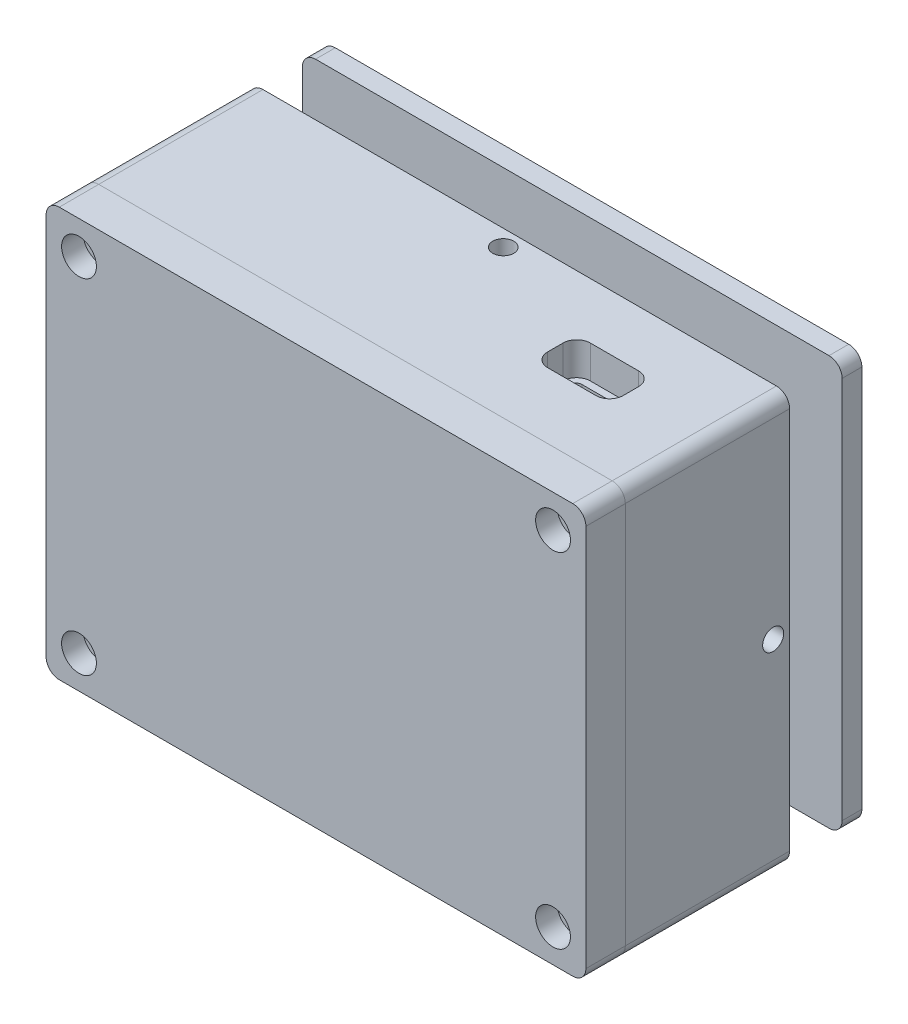
SolidWorks part; units mm, degrees
note: The reader was unsure of these and kept them because the rebuilt part matched: shared geometry of "Sketch8<2>".
ref_plane "Front Plane" through (0, 0, 0) normal (0, 0, 1) x (1, 0, 0)
ref_plane "Top Plane" through (0, 0, 0) normal (0, 1, 0) x (1, 0, 0)
ref_plane "Right Plane" through (0, 0, 0) normal (1, 0, 0) x (0, 0, -1)
sketch "Sketch1" plane through (0, 0, 0) normal (0, 0, 1) x (1, 0, 0)
  line L0 (-52.3117, 23.3251) -> (-52.3117, -26.6749)
  line L1 (-52.3117, -26.6749) -> (17.6883, -26.6749)
  line L2 (17.6883, -26.6749) -> (17.6883, 23.3251)
  line L3 (17.6883, 23.3251) -> (-52.3117, 23.3251)
  dimension "D1" = 50
  dimension "D2" = 70
extrude "Boss-Extrude1" add sketch "Sketch1" along normal blind 2
sketch "Sketch2" plane through (0, 0, 2) normal (0, 0, 1) x (1, 0, 0)
  line L0 (-42.7906, 27.3251) -> (-53.3117, 9.1507)
  line L1 (-53.3117, 9.1507) -> (12.0295, -28.6749)
  line L2 (12.0295, -28.6749) -> (22.5506, -10.5005)
  line L3 (22.5506, -10.5005) -> (-42.7906, 27.3251)
  line L4 (-52.3117, 23.3251) -> (-52.3117, -26.6749) construction
  line L5 (17.6883, 23.3251) -> (-52.3117, 23.3251) construction
  line L7 (-52.3117, -26.6749) -> (17.6883, -26.6749) construction
  dimension "D1" = 21
  dimension "D2" = 75.5
  dimension "D3" = 1
  dimension "D4" = 4
  dimension "D5" = 2
extrude "Boss-Extrude2" add sketch "Sketch2" along normal blind 21
sketch "Sketch3" plane through (0, 0, 0) normal (0, 0, -1) x (-1, 0, 0)
  line L0 (-22.6795, 27.4751) -> (-22.6795, -28.8149)
  line L1 (-22.6795, -28.8149) -> (53.4617, -28.8149)
  line L2 (53.4617, -28.8149) -> (53.4617, 27.4751)
  line L3 (53.4617, 27.4751) -> (-22.6795, 27.4751)
  dimension "D1" = 0.129
  dimension "D2" = 0.14
  dimension "D3" = 0.15
  dimension "D4" = 0.15
extrude "Extrude-Thin1" add sketch "Sketch3" along normal blind 10 and the other way blind 23 separate body thin
sketch "Sketch4" plane through (0, 0, 23) normal (0, 0, 1) x (1, 0, 0)
  line L0 (-42.7906, 27.3251) -> (-53.3117, 9.1507)
  line L1 (-53.3117, 9.1507) -> (12.0295, -28.6749)
  line L2 (12.0295, -28.6749) -> (22.5506, -10.5005)
  line L3 (22.5506, -10.5005) -> (-42.7906, 27.3251)
  line L4 (-53.4617, 27.4751) -> (-53.4617, -28.8149)
  line L5 (-53.4617, -28.8149) -> (22.6795, -28.8149)
  line L6 (22.6795, -28.8149) -> (22.6795, 27.4751)
  line L7 (22.6795, 27.4751) -> (22.6795, -28.8149) construction
  line L8 (22.6795, 27.4751) -> (-53.4617, 27.4751)
extrude "Boss-Extrude3" add sketch "Sketch4" against normal blind 6
fillet "Fillet1" radius 2 4 edges at (25.6795, 30.4751, 6.5) (25.6795, -31.8149, 6.5) (-56.4617, -31.8149, 6.5) (-56.4617, 30.4751, 6.5)
sketch "Sketch5" plane through (0, 0, -10) normal (0, 0, -1) x (-1, 0, 0)
  line L4 (-25.6795, 28.4751) -> (-25.6795, -29.8149) construction
  line L5 (-25.6795, 28.4751) -> (-25.6795, -29.8149)
  line L6 (54.4617, 30.4751) -> (-23.6795, 30.4751) construction
  line L7 (54.4617, 30.4751) -> (-23.6795, 30.4751)
  line L8 (56.4617, -29.8149) -> (56.4617, 28.4751) construction
  line L9 (56.4617, -29.8149) -> (56.4617, 28.4751)
  line L10 (-23.6795, -31.8149) -> (54.4617, -31.8149) construction
  line L11 (-23.6795, -31.8149) -> (54.4617, -31.8149)
  arc A0 (-23.6795, 30.4751) -> (-25.6795, 28.4751) centre (-23.6795, 28.4751) ccw construction
  arc A1 (-23.6795, 30.4751) -> (-25.6795, 28.4751) centre (-23.6795, 28.4751) ccw
  arc A2 (56.4617, 28.4751) -> (54.4617, 30.4751) centre (54.4617, 28.4751) ccw construction
  arc A3 (56.4617, 28.4751) -> (54.4617, 30.4751) centre (54.4617, 28.4751) ccw
  arc A4 (54.4617, -31.8149) -> (56.4617, -29.8149) centre (54.4617, -29.8149) ccw construction
  arc A5 (54.4617, -31.8149) -> (56.4617, -29.8149) centre (54.4617, -29.8149) ccw
  arc A6 (-25.6795, -29.8149) -> (-23.6795, -31.8149) centre (-23.6795, -29.8149) ccw construction
  arc A7 (-25.6795, -29.8149) -> (-23.6795, -31.8149) centre (-23.6795, -29.8149) ccw
extrude "Boss-Extrude4" add sketch "Sketch5" along normal blind 3 separate body
sketch "Sketch6" plane through (0, 0, 17) normal (0, 0, -1) x (-1, 0, 0)
  line L0 (-16.6795, 27.4751) -> (-22.6795, 22.5325)
  line L1 (-22.6795, 27.4751) -> (53.4617, 27.4751) construction
  line L2 (-22.6795, 27.4751) -> (-22.6795, -28.8149) construction
  line L3 (-22.6795, 22.5325) -> (-22.6795, 27.4751)
  line L4 (-22.6795, 27.4751) -> (-16.6795, 27.4751)
  line L5 (42.7906, 27.3251) -> (53.3117, 9.1507)
  line L6 (53.3117, 9.1507) -> (53.4617, 27.4751)
  line L8 (-12.0295, -28.6749) -> (-22.5506, -10.5005)
  line L11 (53.4617, -25.8149) -> (-7.0891, -25.8149)
  line L12 (53.4617, -28.8149) -> (53.4617, 27.4751) construction
  line L13 (53.3117, 9.1507) -> (-12.0295, -28.6749) construction
  line L15 (53.4617, -28.8149) -> (53.4617, -25.8149)
  line L16 (53.4617, -28.8149) -> (-22.6795, -28.8149) construction
  line L18 (-22.6795, -28.8149) -> (53.4617, -28.8149)
  line L19 (-7.0891, -25.8149) -> (-12.0295, -28.6749)
  line L20 (-22.5506, -10.5005) -> (-22.6795, -10.5005)
  line L21 (-22.6795, -10.5005) -> (-22.6795, -28.8149)
  line L22 (42.7906, 27.3251) -> (42.7906, 27.4751)
  line L23 (42.7906, 27.4751) -> (53.4617, 27.4751)
  dimension "D1" = 6
  dimension "D2" = 3
extrude "Boss-Extrude8" add sketch "Sketch6" along normal blind 10
sketch "Sketch7" plane through (0, 0, -10) normal (0, 0, -1) x (-1, 0, 0)
  line L0 (-28.6149, 33.2878) -> (-28.6149, -37.3908)
  line L1 (-28.6149, -37.3908) -> (75.8219, -37.3908)
  line L2 (75.8219, -37.3908) -> (71.6241, 45.1665)
  line L3 (71.6241, 45.1665) -> (-28.6149, 33.2878)
extrude "Cut-Extrude1" cut sketch "Sketch7" against normal blind 8
sketch "Sketch8" plane through (0, 30.4751, 0) normal (0, 1, 0) x (1, 0, 0)
  line L0 (1.7795, -8.5741) -> (1.7795, -10.9259)
  line L1 (3.8536, -13) -> (11.2055, -13)
  line L2 (13.2795, -10.9259) -> (13.2795, -8.5741)
  line L3 (11.2055, -6.5) -> (3.8536, -6.5)
  line L4 (-54.4617, -23) -> (23.6795, -23) construction
  line L6 (25.6795, 2) -> (25.6795, -23) construction
  arc A0 (11.2055, -13) -> (13.2795, -10.9259) centre (11.2055, -10.9259) ccw
  arc A1 (13.2795, -8.5741) -> (11.2055, -6.5) centre (11.2055, -8.5741) ccw
  arc A2 (3.8536, -13) -> (1.7795, -10.9259) centre (3.8536, -10.9259) cw
  arc A3 (3.8536, -6.5) -> (1.7795, -8.5741) centre (3.8536, -8.5741) ccw
  point P12 (13.2795, -6.5)
  point P15 (1.7795, -13)
  point P18 (1.7795, -6.5)
  dimension "D5" = 2.0741
  dimension "D6" = 2.0741
  dimension "D7" = 2.0741
  dimension "D8" = 2.0741
  dimension "D1" = 11.5
  dimension "D2" = 6.5
  dimension "D3" = 10
  dimension "D4" = 12.4
extrude "Cut-Extrude2" cut sketch "Sketch8" against normal blind 8
extrude "Extrude-Thin2" add sketch "Sketch8<2>" against normal blind 6 thin
sketch "Sketch8<2>" plane through (0, 30.4751, 0) normal (0, 1, 0) x (1, 0, 0) same geometry as "Sketch8"
sketch "Sketch10" plane through (0, 27.4751, 0) normal (0, -1, 0) x (1, 0, 0)
  line L0 (1.7795, 9.75) -> (13.2795, 9.75) construction
  line L1 (1.7795, 8.5741) -> (1.7795, 10.9259) construction
  line L2 (13.2795, 10.9259) -> (13.2795, 8.5741) construction
  line L3 (7.5295, 13) -> (7.5295, 6.5) construction
  line L4 (3.8536, 13) -> (11.2055, 13) construction
  line L5 (11.2055, 6.5) -> (3.8536, 6.5) construction
  line L6 (3.6795, 11.9) -> (11.3795, 11.9)
  line L7 (12.3795, 10.9) -> (12.3795, 8.6)
  line L8 (11.3795, 7.6) -> (3.6795, 7.6)
  line L9 (2.6795, 8.6) -> (2.6795, 10.9)
  line L10 (1.7795, 8.5741) -> (1.7795, 10.9259)
  line L11 (11.2055, 6.5) -> (3.8536, 6.5)
  line L12 (13.2795, 10.9259) -> (13.2795, 8.5741)
  line L13 (3.8536, 13) -> (11.2055, 13)
  arc A0 (1.7795, 8.5741) -> (3.8536, 6.5) centre (3.8536, 8.5741) ccw construction
  arc A1 (11.2055, 6.5) -> (13.2795, 8.5741) centre (11.2055, 8.5741) ccw construction
  arc A2 (13.2795, 10.9259) -> (11.2055, 13) centre (11.2055, 10.9259) ccw construction
  arc A3 (3.8536, 13) -> (1.7795, 10.9259) centre (3.8536, 10.9259) ccw construction
  arc A4 (1.7795, 8.5741) -> (3.8536, 6.5) centre (3.8536, 8.5741) ccw
  arc A5 (11.2055, 6.5) -> (13.2795, 8.5741) centre (11.2055, 8.5741) ccw
  arc A6 (13.2795, 10.9259) -> (11.2055, 13) centre (11.2055, 10.9259) ccw
  arc A7 (3.8536, 13) -> (1.7795, 10.9259) centre (3.8536, 10.9259) ccw
  arc A8 (11.3795, 11.9) -> (12.3795, 10.9) centre (11.3795, 10.9) cw
  arc A9 (12.3795, 8.6) -> (11.3795, 7.6) centre (11.3795, 8.6) cw
  arc A10 (3.6795, 7.6) -> (2.6795, 8.6) centre (3.6795, 8.6) cw
  arc A11 (3.6795, 11.9) -> (2.6795, 10.9) centre (3.6795, 10.9) ccw
  point P11 (12.3795, 11.9)
  point P27 (2.6795, 7.6)
  point P30 (2.6795, 11.9)
  dimension "D3" = 1
  dimension "D4" = 1
  dimension "D5" = 1
  dimension "D6" = 1
  dimension "D1" = 4.3
  dimension "D2" = 9.7
extrude "Boss-Extrude9" add sketch "Sketch10" along normal blind 1 from offset 2
fillet "Fillet2" radius 3 6 edges at (7.5295, 24.4751, 15) (14.0863, 24.4751, 13.8067) (14.0863, 24.4751, 5.6933) (7.5295, 24.4751, 4.5) (0.9728, 24.4751, 5.6933) (0.9728, 24.4751, 13.8067)
sketch "Sketch11" plane through (0, 0, 23) normal (0, 0, 1) x (1, 0, 0)
  line L0 (-51.4617, 30.4751) -> (-51.4617, -31.8149) construction
  line L1 (-54.4617, 30.4751) -> (23.6795, 30.4751) construction
  line L2 (23.6795, -31.8149) -> (-54.4617, -31.8149) construction
  line L3 (20.6795, 30.4751) -> (20.6795, -31.8149) construction
  line L4 (-15.3911, 30.4751) -> (-15.3911, -31.8149) construction
  line L5 (-56.4617, -0.6699) -> (25.6795, -0.6699) construction
  line L6 (-56.4617, -29.8149) -> (-56.4617, 28.4751) construction
  line L7 (25.6795, 28.4751) -> (25.6795, -29.8149) construction
  circle A0 centre (-51.4617, 25.4751) radius 1.8
  circle A1 centre (-51.4617, -26.8149) radius 1.8
  circle A2 centre (20.6795, -26.8149) radius 1.8
  circle A3 centre (20.6795, 25.4751) radius 1.8
  dimension "D3" = 3.6
  dimension "D1" = 5
  dimension "D2" = 5
  dimension "D4" = 5
extrude "Cut-Extrude3" cut sketch "Sketch11" against normal blind 5
sketch "Sketch12" plane through (0, 30.4751, 0) normal (0, 1, 0) x (1, 0, 0)
  line L0 (-15.3911, 2) -> (-15.3911, -23) construction
  line L1 (-54.4617, 2) -> (23.6795, 2) construction
  line L2 (-54.4617, -23) -> (23.6795, -23) construction
  circle A0 centre (-15.3911, -0.5) radius 1.6
  dimension "D1" = 3.2
  dimension "D2" = 2.5
extrude "Cut-Extrude4" cut sketch "Sketch12" against normal through all both and the other way through all
sketch "Sketch13" plane through (25.6795, 0, 0) normal (1, 0, 0) x (0, 0, -1)
  line L0 (-23, -0.6699) -> (2, -0.6699) construction
  line L1 (-23, 28.4751) -> (-23, -29.8149) construction
  line L2 (2, 28.4751) -> (2, -29.8149) construction
  circle A0 centre (-0.5, -0.6699) radius 1.6
  dimension "D1" = 3.2
  dimension "D2" = 2.5
extrude "Cut-Extrude5" cut sketch "Sketch13" against normal through all both
sketch "Sketch14" plane through (0, 0, 23) normal (0, 0, 1) x (1, 0, 0)
  line L0 (-42.7906, 27.3251) -> (-53.3117, 9.1507)
  line L1 (-53.3117, 9.1507) -> (12.0295, -28.6749)
  line L2 (12.0295, -28.6749) -> (22.5506, -10.5005)
  line L3 (22.5506, -10.5005) -> (-42.7906, 27.3251)
  line L4 (23.6795, -31.8149) -> (-54.4617, -31.8149) construction
  line L5 (25.6795, 28.4751) -> (25.6795, -29.8149) construction
  line L6 (-54.4617, 30.4751) -> (23.6795, 30.4751) construction
  line L7 (-56.4617, -29.8149) -> (-56.4617, 28.4751) construction
  line L8 (23.6795, -31.8149) -> (-54.4617, -31.8149)
  line L9 (25.6795, 28.4751) -> (25.6795, -29.8149)
  line L10 (-54.4617, 30.4751) -> (23.6795, 30.4751)
  line L11 (-56.4617, -29.8149) -> (-56.4617, 28.4751)
  arc A0 (-56.4617, -29.8149) -> (-54.4617, -31.8149) centre (-54.4617, -29.8149) ccw construction
  arc A1 (23.6795, -31.8149) -> (25.6795, -29.8149) centre (23.6795, -29.8149) ccw construction
  arc A2 (25.6795, 28.4751) -> (23.6795, 30.4751) centre (23.6795, 28.4751) ccw construction
  arc A3 (-54.4617, 30.4751) -> (-56.4617, 28.4751) centre (-54.4617, 28.4751) ccw construction
  arc A4 (-56.4617, -29.8149) -> (-54.4617, -31.8149) centre (-54.4617, -29.8149) ccw
  arc A5 (23.6795, -31.8149) -> (25.6795, -29.8149) centre (23.6795, -29.8149) ccw
  arc A6 (25.6795, 28.4751) -> (23.6795, 30.4751) centre (23.6795, 28.4751) ccw
  arc A7 (-54.4617, 30.4751) -> (-56.4617, 28.4751) centre (-54.4617, 28.4751) ccw
  circle A8 centre (-51.4617, 25.4751) radius 1.6
  circle A9 centre (20.6795, 25.4751) radius 1.6
  circle A10 centre (-51.4617, -26.8149) radius 1.6
  circle A11 centre (20.6795, -26.8149) radius 1.6
  dimension "D1" = 3.2
extrude "Boss-Extrude10" add sketch "Sketch14" along normal blind 5 separate body
sketch "Sketch15" plane through (0, 0, 28) normal (0, 0, 1) x (1, 0, 0)
  line L0 (-56.4617, 28.4751) -> (-56.4617, -29.8149)
  line L1 (-54.4617, -31.8149) -> (23.6795, -31.8149) construction
  line L2 (-54.4617, -31.8149) -> (23.6795, -31.8149)
  line L3 (25.6795, -29.8149) -> (25.6795, 28.4751) construction
  line L4 (25.6795, -29.8149) -> (25.6795, 28.4751)
  line L5 (23.6795, 30.4751) -> (-54.4617, 30.4751) construction
  line L6 (23.6795, 30.4751) -> (-54.4617, 30.4751)
  arc A0 (-56.4617, -29.8149) -> (-54.4617, -31.8149) centre (-54.4617, -29.8149) ccw construction
  arc A1 (-56.4617, -29.8149) -> (-54.4617, -31.8149) centre (-54.4617, -29.8149) ccw
  arc A2 (23.6795, -31.8149) -> (25.6795, -29.8149) centre (23.6795, -29.8149) ccw construction
  arc A3 (23.6795, -31.8149) -> (25.6795, -29.8149) centre (23.6795, -29.8149) ccw
  arc A4 (25.6795, 28.4751) -> (23.6795, 30.4751) centre (23.6795, 28.4751) ccw construction
  arc A5 (25.6795, 28.4751) -> (23.6795, 30.4751) centre (23.6795, 28.4751) ccw
  arc A6 (-54.4617, 30.4751) -> (-56.4617, 28.4751) centre (-54.4617, 28.4751) ccw construction
  arc A7 (-54.4617, 30.4751) -> (-56.4617, 28.4751) centre (-54.4617, 28.4751) ccw
extrude "Boss-Extrude11" add sketch "Sketch15" along normal blind 1
chamfer "Chamfer1" distance 4 angle 30 2 edges at (-20.6411, -9.7621, 23) (-10.12, 8.4123, 23)
sketch "Sketch16" plane through (0, 0, 23) normal (0, 0, -1) x (-1, 0, 0)
  circle A0 centre (-20.6795, 25.4751) radius 1.6
  circle A1 centre (51.4617, -26.8149) radius 1.6
  circle A2 centre (-20.6795, -26.8149) radius 1.6
  circle A3 centre (51.4617, 25.4751) radius 1.6
extrude "Cut-Extrude6" cut sketch "Sketch16" against normal through all
sketch "Sketch17" plane through (0, 0, 29) normal (0, 0, 1) x (1, 0, 0)
  circle A0 centre (-51.4617, 25.4751) radius 2.65
  circle A1 centre (-51.4617, -26.8149) radius 2.65
  circle A2 centre (20.6795, 25.4751) radius 2.65
  circle A3 centre (20.6795, -26.8149) radius 2.65
  dimension "D1" = 5.3
extrude "Cut-Extrude7" cut sketch "Sketch17" against normal blind 3.3
